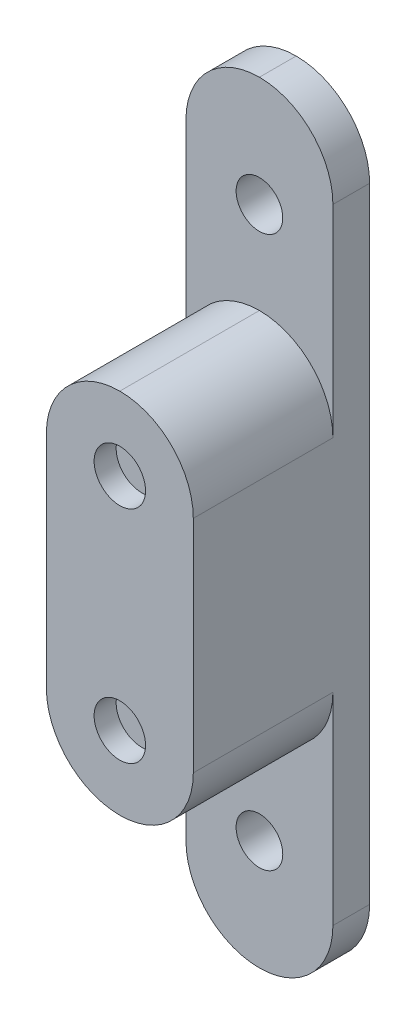
SolidWorks part; units mm, degrees
ref_plane "Front" through (0, 0, 0) normal (0, 0, 1) x (1, 0, 0)
ref_plane "Top" through (0, 0, 0) normal (0, 1, 0) x (1, 0, 0)
ref_plane "Right" through (0, 0, 0) normal (1, 0, 0) x (0, 0, -1)
sketch "Sketch1" plane through (0, 0, 0) normal (0, 0, 1) x (1, 0, 0)
  line L1 (-10, -52.5) -> (10, -52.5)
  line L2 (-10, -52.5) -> (-10, 52.5)
  line L3 (-10, 52.5) -> (10, 52.5)
  line L4 (10, -52.5) -> (10, 52.5)
  line L5 (-10, -52.5) -> (10, 52.5) construction
  line L6 (-10, 52.5) -> (10, -52.5) construction
  point P0 (0, 0)
  dimension "D1" = 20
  dimension "D2" = 105
extrude "Boss-Extrude1" add sketch "Sketch1" along normal blind 5
sketch "Sketch2" plane through (0, 0, 5) normal (0, 0, 1) x (1, 0, 0)
  line L0 (0, -37.5) -> (0, 37.5) construction
  circle A0 centre (0, 37.5) radius 3.175
  circle A1 centre (0, -37.5) radius 3.175
  point P4 (0, 0)
  dimension "D1" = 6.35
  dimension "D2" = 75
extrude "Cut-Extrude1" cut sketch "Sketch2" against normal through all
sketch "Sketch4" plane through (0, 0, 5) normal (0, 0, 1) x (1, 0, 0)
  line L0 (-10, 52.5) -> (-10, -52.5) construction
  line L1 (10, 25) -> (-10, 25)
  line L2 (10, 25) -> (10, -25)
  line L3 (10, -25) -> (-10, -25)
  line L4 (-10, 25) -> (-10, -25)
  line L5 (10, 25) -> (-10, -25) construction
  line L6 (10, -25) -> (-10, 25) construction
  point P0 (0, 0)
  dimension "D1" = 50
extrude "Boss-Extrude3" add sketch "Sketch4" along normal blind 19
sketch "Sketch5" plane through (0, 0, 24) normal (0, 0, 1) x (1, 0, 0)
  line L0 (0, -15) -> (0, 15) construction
  circle A0 centre (0, -15) radius 3.5
  circle A1 centre (0, 15) radius 3.5
  point P4 (0, 0)
  dimension "D1" = 7
  dimension "D2" = 30
extrude "Cut-Extrude2" cut sketch "Sketch5" against normal blind 3
fillet "Fillet5" radius 10 8 edges at (10, -52.5, 2.5) (-10, -52.5, 2.5) (10, -25, 14.5) (-10, -25, 14.5) (10, 25, 14.5) (-10, 25, 14.5) (-10, 52.5, 2.5) (10, 52.5, 2.5)
